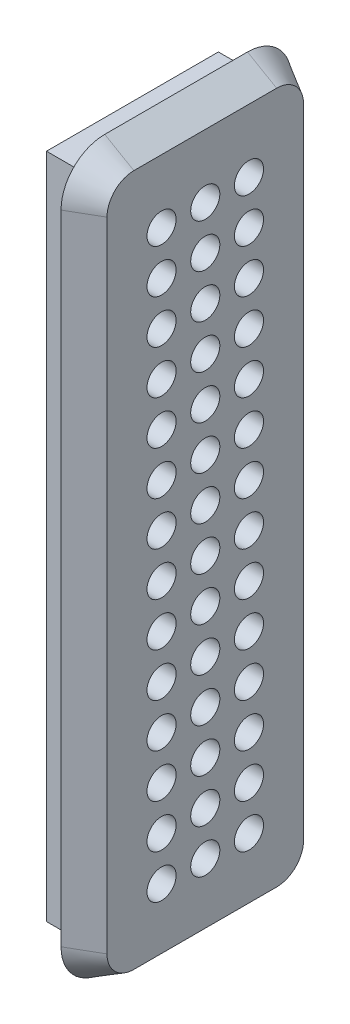
SolidWorks part; units mm, degrees
ref_plane "前视基准面" through (0, 0, 0) normal (0, 0, 1) x (1, 0, 0)
ref_plane "上视基准面" through (0, 0, 0) normal (0, 1, 0) x (1, 0, 0)
ref_plane "右视基准面" through (0, 0, 0) normal (1, 0, 0) x (0, 0, -1)
other "Configuration Table"
sketch "草图1" plane through (0, 0, 0) normal (1, 0, 0) x (0, 0, -1)
  line L0 (-147.2592, 68.0612) -> (-135.4592, 68.0612)
  line L1 (-147.3592, 68.1612) -> (-135.3592, 68.1612) construction
  line L2 (-147.3592, 68.1612) -> (-147.3592, 22.1612) construction
  line L3 (-147.3592, 22.1612) -> (-135.3592, 22.1612) construction
  line L4 (-135.3592, 68.1612) -> (-135.3592, 22.1612) construction
  line L5 (-135.4592, 68.0612) -> (-135.4592, 22.2612)
  line L6 (-147.2592, 22.2612) -> (-135.4592, 22.2612)
  line L7 (-147.2592, 68.0612) -> (-147.2592, 22.2612)
  line L8 (-145.7592, 66.5612) -> (-145.7592, 23.7612)
  line L9 (-145.7592, 23.7612) -> (-136.9592, 23.7612)
  line L10 (-136.9592, 66.5612) -> (-136.9592, 23.7612)
  line L11 (-145.7592, 66.5612) -> (-136.9592, 66.5612)
  dimension "D1" = 12
  dimension "D2" = 46
  dimension "D3" = 0.1
  dimension "D4" = 1.5
extrude "凸台-拉伸1" add sketch "草图1" along normal blind 3
sketch "草图2" plane through (3, 0, 0) normal (1, 0, 0) x (0, 0, -1)
  line L12 (-149.2592, 20.2612) -> (-133.4592, 20.2612)
  line L13 (-149.2592, 70.0612) -> (-149.2592, 20.2612)
  line L14 (-133.4592, 70.0612) -> (-149.2592, 70.0612)
  line L15 (-133.4592, 20.2612) -> (-133.4592, 70.0612)
  line L16 (-146.2592, 20.2612) -> (-136.4592, 20.2612)
  line L17 (-149.2592, 67.0612) -> (-149.2592, 23.2612)
  line L18 (-136.4592, 70.0612) -> (-146.2592, 70.0612)
  line L19 (-133.4592, 23.2612) -> (-133.4592, 67.0612)
  arc A0 (-136.4592, 70.0612) -> (-133.4592, 67.0612) centre (-136.4592, 67.0612) cw
  arc A1 (-136.4592, 20.2612) -> (-133.4592, 23.2612) centre (-136.4592, 23.2612) ccw
  arc A2 (-146.2592, 20.2612) -> (-149.2592, 23.2612) centre (-146.2592, 23.2612) cw
  arc A3 (-149.2592, 67.0612) -> (-146.2592, 70.0612) centre (-146.2592, 67.0612) cw
  dimension "D2" = 3
  dimension "D1" = 2
extrude "凸台-拉伸2" add sketch "草图2" along normal blind 2 draft 30
sketch "草图3" plane through (3, 0, 0) normal (-1, 0, 0) x (0, 0, 1)
  line L0 (136.4592, 70.0612) -> (146.2592, 70.0612) construction
  circle A1 centre (144.3592, 64.5612) radius 1
  circle A2 centre (141.3592, 64.5612) radius 1
  circle A3 centre (138.3592, 64.5612) radius 1
  circle A4 centre (141.3592, 61.5612) radius 1
  circle A5 centre (138.3592, 61.5612) radius 1
  circle A6 centre (141.3592, 58.5612) radius 1
  circle A7 centre (138.3592, 58.5612) radius 1
  circle A8 centre (141.3592, 55.5612) radius 1
  circle A9 centre (138.3592, 55.5612) radius 1
  circle A10 centre (141.3592, 52.5612) radius 1
  circle A11 centre (138.3592, 52.5612) radius 1
  circle A12 centre (141.3592, 49.5612) radius 1
  circle A13 centre (138.3592, 49.5612) radius 1
  circle A14 centre (141.3592, 46.5612) radius 1
  circle A15 centre (138.3592, 46.5612) radius 1
  circle A16 centre (141.3592, 43.5612) radius 1
  circle A17 centre (138.3592, 43.5612) radius 1
  circle A18 centre (141.3592, 40.5612) radius 1
  circle A19 centre (138.3592, 40.5612) radius 1
  circle A20 centre (141.3592, 37.5612) radius 1
  circle A21 centre (138.3592, 37.5612) radius 1
  circle A22 centre (141.3592, 34.5612) radius 1
  circle A23 centre (138.3592, 34.5612) radius 1
  circle A24 centre (141.3592, 31.5612) radius 1
  circle A25 centre (138.3592, 31.5612) radius 1
  circle A26 centre (141.3592, 28.5612) radius 1
  circle A27 centre (138.3592, 28.5612) radius 1
  circle A28 centre (141.3592, 25.5612) radius 1
  circle A29 centre (138.3592, 25.5612) radius 1
  circle A30 centre (144.3592, 61.5612) radius 1
  circle A31 centre (144.3592, 58.5612) radius 1
  circle A32 centre (144.3592, 55.5612) radius 1
  circle A33 centre (144.3592, 52.5612) radius 1
  circle A34 centre (144.3592, 49.5612) radius 1
  circle A35 centre (144.3592, 46.5612) radius 1
  circle A36 centre (144.3592, 43.5612) radius 1
  circle A37 centre (144.3592, 40.5612) radius 1
  circle A38 centre (144.3592, 37.5612) radius 1
  circle A39 centre (144.3592, 34.5612) radius 1
  circle A40 centre (144.3592, 31.5612) radius 1
  circle A41 centre (144.3592, 28.5612) radius 1
  circle A42 centre (144.3592, 25.5612) radius 1
  point P4 (141.3592, 70.0612)
  dimension "D1" = 2
  dimension "D2" = 5.5
  dimension "D4" = 3
  dimension "D5" = 14
extrude "切除-拉伸1" cut sketch "草图3" against normal up to next (2 mm away)
